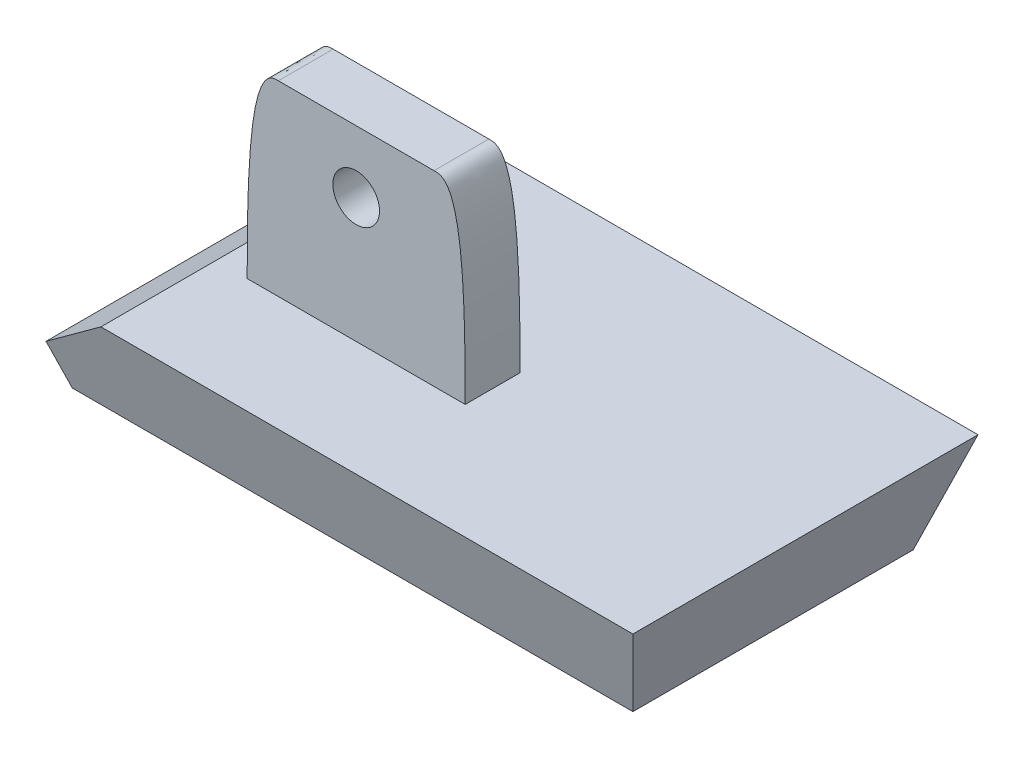
SolidWorks part; units mm, degrees
ref_plane "Ebene vorne" through (0, 0, 0) normal (0, 0, 1) x (1, 0, 0)
ref_plane "Ebene oben" through (0, 0, 0) normal (0, 1, 0) x (1, 0, 0)
ref_plane "Ebene rechts" through (0, 0, 0) normal (1, 0, 0) x (0, 0, -1)
sketch "Skizze1" plane through (0, 0, 0) normal (0, 1, 0) x (1, 0, 0)
  line L1 (-90, -45) -> (90, -45)
  line L2 (-90, -45) -> (-90, 45)
  line L3 (-90, 45) -> (90, 45)
  line L4 (90, -45) -> (90, 45)
  line L5 (-90, -45) -> (90, 45) construction
  line L6 (-90, 45) -> (90, -45) construction
  point P0 (0, 0)
  dimension "D1" = 180
  dimension "D2" = 90
extrude "Aufsatz-Linear austragen1" add sketch "Skizze1" along normal blind 32 draft 18 draft outward yes
sketch "Skizze2" plane through (0, 32, 0) normal (0, 1, 0) x (1, 0, 0)
  line L1 (-60.3451, -0.8985) -> (9.6549, -0.8985)
  line L2 (-60.3451, -0.8985) -> (-60.3451, -18.4986)
  line L3 (-60.3451, -18.4986) -> (9.6549, -18.4986)
  line L4 (9.6549, -0.8985) -> (9.6549, -18.4986)
  dimension "D1" = 70
extrude "Aufsatz-Linear austragen2" add sketch "Skizze2" along normal blind 60
sketch "Skizze3" plane through (0, 0, 0.8985) normal (0, 0, -1) x (-1, 0, 0)
  line L0 (-9.6549, 32) -> (60.3451, 32) construction
  circle A0 centre (25.3451, 72) radius 7.5
  point P4 (25.3451, 32)
  dimension "D1" = 15
  dimension "D2" = 40
extrude "Schnitt-Linear austragen1" cut sketch "Skizze3" against normal up to surface (17.6001 mm away) up to face at (-25.3451, 62, 18.4986)
fillet "Verrundung1" radius 60 2 edges at (9.6549, 92, 9.6985) (-60.3451, 92, 9.6985) curvature continuous yes second distance 10 first distance on face at (9.6549, 62, 9.6985) first distance on face at (-60.3451, 62, 9.6985)
chamfer "Fase1" distance 20 distance2 30 1 edges at (-100.3974, 32, 0) first distance on face at (-95.1987, 16, 0)
move or copy body "Körper-Verschieben/Kopieren1" [suppressed] bodies to move or copy 103
